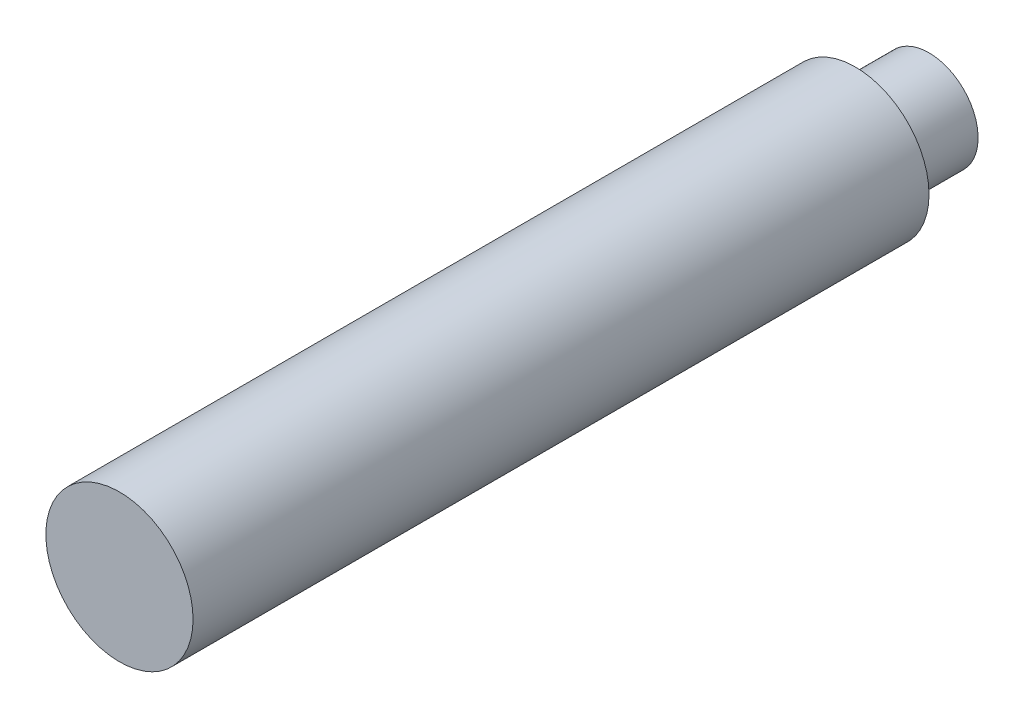
SolidWorks part; units mm, degrees
ref_plane "Front Plane" through (0, 0, 0) normal (0, 0, 1) x (1, 0, 0)
ref_plane "Top Plane" through (0, 0, 0) normal (0, 1, 0) x (1, 0, 0)
ref_plane "Right Plane" through (0, 0, 0) normal (1, 0, 0) x (0, 0, -1)
sketch "Sketch1" plane through (0, 0, 0) normal (0, 0, 1) x (1, 0, 0)
  circle A0 centre (0, 0) radius 3
  dimension "D1" = 6
extrude "Boss-Extrude1" add sketch "Sketch1" along normal blind 30 contours A0
sketch "Sketch2" plane through (0, 0, 0) normal (0, 0, -1) x (-1, 0, 0)
  circle A0 centre (0, 0) radius 2
  dimension "D1" = 4
extrude "Boss-Extrude2" add sketch "Sketch2" along normal blind 3
